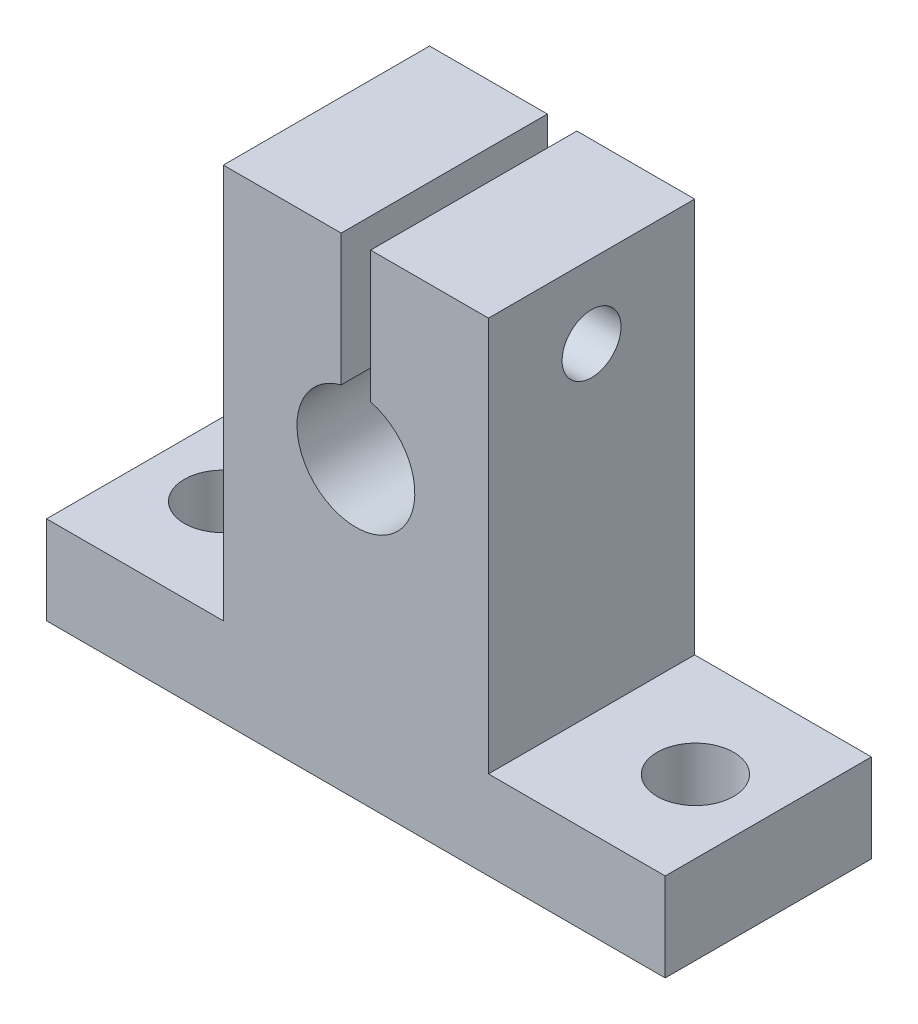
SolidWorks part; units mm, degrees
material "6063-O"
ref_plane "Alzado" through (0, 0, 0) normal (0, 0, 1) x (1, 0, 0)
ref_plane "Planta" through (0, 0, 0) normal (0, 1, 0) x (1, 0, 0)
ref_plane "Vista lateral" through (0, 0, 0) normal (1, 0, 0) x (0, 0, -1)
sketch "Croquis1" plane through (0, 0, 0) normal (0, 0, 1) x (1, 0, 0)
  line L0 (0, 32.8) -> (0, 0) construction
  line L2 (-9, 6) -> (-9, 32.8)
  line L3 (-9, 32.8) -> (9, 32.8)
  line L4 (9, 6) -> (9, 32.8)
  line L5 (21, 0) -> (-21, 0)
  line L6 (21, 0) -> (21, 6)
  line L7 (21, 6) -> (9, 6)
  line L8 (-21, 0) -> (-21, 6)
  line L9 (-9, 6) -> (-21, 6)
  dimension "D1" = 42
  dimension "D2" = 21
  dimension "D3" = 18
  dimension "D4" = 32.8
  dimension "D5" = 6
extrude "Saliente-Extruir1" add sketch "Croquis1" along normal blind 14
sketch "Croquis2" plane through (0, 6, 0) normal (0, 1, 0) x (1, 0, 0)
  line L0 (-16.05, -7) -> (16.05, -7) construction
  line L4 (-21, -14) -> (-21, 0) construction
  circle A0 centre (-16.05, -7) radius 2.6
  circle A1 centre (16.05, -7) radius 2.6
  point P4 (0, -7)
  point P7 (-21, -7)
  dimension "D1" = 5.2
  dimension "D2" = 5.2
  dimension "D3" = 37.3
extrude "Cortar-Extruir1" cut sketch "Croquis2" against normal blind 14
sketch "Croquis3" plane through (0, 0, 14) normal (0, 0, 1) x (1, 0, 0)
  line L0 (-1, 23.873) -> (-1, 32.8)
  line L1 (9, 32.8) -> (-9, 32.8) construction
  line L2 (1, 32.8) -> (1, 23.873)
  line L3 (-1, 32.8) -> (1, 32.8)
  arc A0 (-1, 23.873) -> (1, 23.873) centre (0, 20) ccw
  dimension "D1" = 8
  dimension "D2" = 20
  dimension "D3" = 2
extrude "Cortar-Extruir2" cut sketch "Croquis3" against normal through all
ref_axis "Eje1" through (0, 20, 0) along (0, 0, 1)
sketch "Croquis4" plane through (-9, 0, 0) normal (-1, 0, 0) x (0, 0, 1)
  line L0 (0, 20) -> (14, 20) construction
  line L1 (14, 32.8) -> (0, 32.8) construction
  circle A0 centre (7, 27.8) radius 2
  point P8 (7, 32.8)
  dimension "D2" = 4
  dimension "D1" = 7.8
extrude "Cortar-Extruir3" cut sketch "Croquis4" against normal through all
